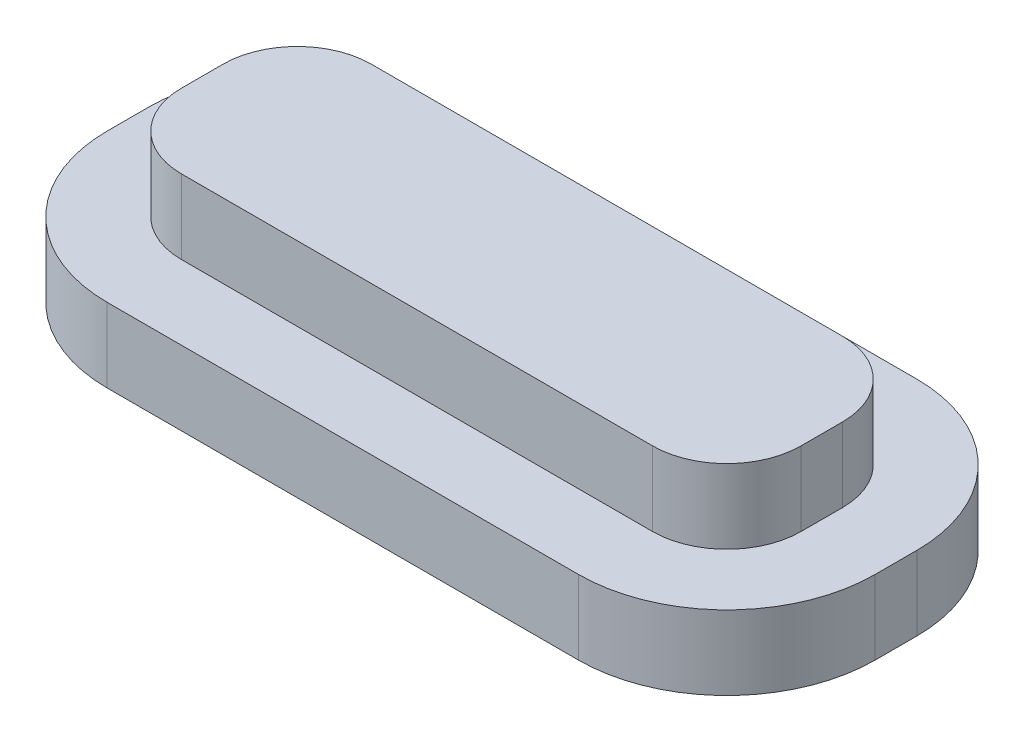
SolidWorks part; units mm, degrees
ref_plane "Front Plane" through (0, 0, 0) normal (0, 0, 1) x (1, 0, 0)
ref_plane "Top Plane" through (0, 0, 0) normal (0, 1, 0) x (1, 0, 0)
ref_plane "Right Plane" through (0, 0, 0) normal (1, 0, 0) x (0, 0, -1)
sketch "Sketch1" plane through (0, 0, 0) normal (0, 1, 0) x (1, 0, 0)
  line L0 (-3.175, 2.28) -> (3.175, 2.28)
  line L1 (-3.175, -1.28) -> (3.175, -1.28)
  line L2 (-4.175, -0.28) -> (-4.175, 0.28)
  line L3 (-3.175, 1.28) -> (3.175, 1.28)
  line L4 (4.175, -0.28) -> (4.175, 0.28)
  line L5 (-4.175, -1.28) -> (4.175, 1.28) construction
  line L6 (-4.175, 1.28) -> (4.175, -1.28) construction
  line L7 (5.175, -0.28) -> (5.175, 0.28)
  line L8 (-3.175, -2.28) -> (3.175, -2.28)
  line L9 (-5.175, -0.28) -> (-5.175, 0.28)
  arc A0 (-4.175, 0.28) -> (-3.175, 1.28) centre (-3.175, 0.28) cw
  arc A1 (-3.175, -1.28) -> (-4.175, -0.28) centre (-3.175, -0.28) cw
  arc A2 (3.175, -1.28) -> (4.175, -0.28) centre (3.175, -0.28) ccw
  arc A3 (3.175, 1.28) -> (4.175, 0.28) centre (3.175, 0.28) cw
  arc A4 (3.175, 2.28) -> (5.175, 0.28) centre (3.175, 0.28) cw
  arc A5 (3.175, -2.28) -> (5.175, -0.28) centre (3.175, -0.28) ccw
  arc A6 (-3.175, -2.28) -> (-5.175, -0.28) centre (-3.175, -0.28) cw
  arc A7 (-5.175, 0.28) -> (-3.175, 2.28) centre (-3.175, 0.28) cw
  point P0 (0, 0)
  dimension "D1" = 1
  dimension "D3" = 8.35
  dimension "D2" = 2.56
  dimension "D4" = 1
extrude "Boss-Extrude1" add sketch "Sketch1" along normal blind 1
extrude "Boss-Extrude2" add sketch "Sketch1<2>" along normal blind 2 contours A3 L3 A0 L2 A1 L1 A2 L4 region at (0, 0, 0)
sketch "Sketch1<2>" plane through (0, 0, 0) normal (0, 1, 0) x (1, 0, 0) same geometry as "Sketch1"
